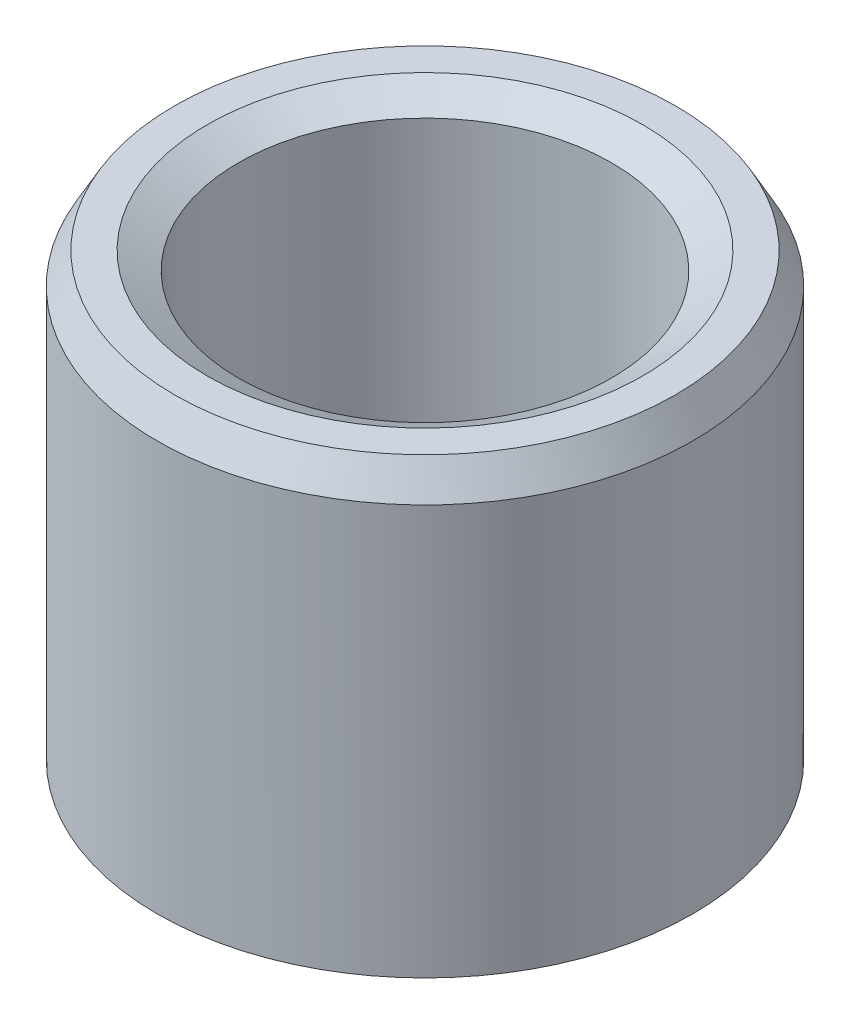
SolidWorks part; units mm, degrees
ref_plane "Front Plane" through (0, 0, 0) normal (0, 0, 1) x (1, 0, 0)
ref_plane "Top Plane" through (0, 0, 0) normal (0, 1, 0) x (1, 0, 0)
ref_plane "Right Plane" through (0, 0, 0) normal (1, 0, 0) x (0, 0, -1)
sketch "Sketch1" plane through (0, 0, 0) normal (0, 1, 0) x (1, 0, 0)
  circle A0 centre (0, 0) radius 27.5
  dimension "SLEEVE_OD" = 55
extrude "Boss-Extrude1" add sketch "Sketch1" along normal blind 47.0515
sketch "Sketch2" plane through (0, 0, 0) normal (0, 1, 0) x (1, 0, 0)
  circle A0 centre (0, 0) radius 19.1563
  dimension "BORE_D" = 38.3126
extrude "Cut-Extrude1" cut sketch "Sketch2" along normal through all
chamfer "Chamfer1" distance 3.2018 angle 29.154 4 edges at (0, 47.0515, 19.1563) (0, 0, 19.1563) (0, 0, 27.5) (0, 47.0515, 27.5) first distance on face at (0, 47.0515, 19.1563) first distance on face at (0, 0, 19.1563) first distance on face at (0, 47.0515, 27.5)
